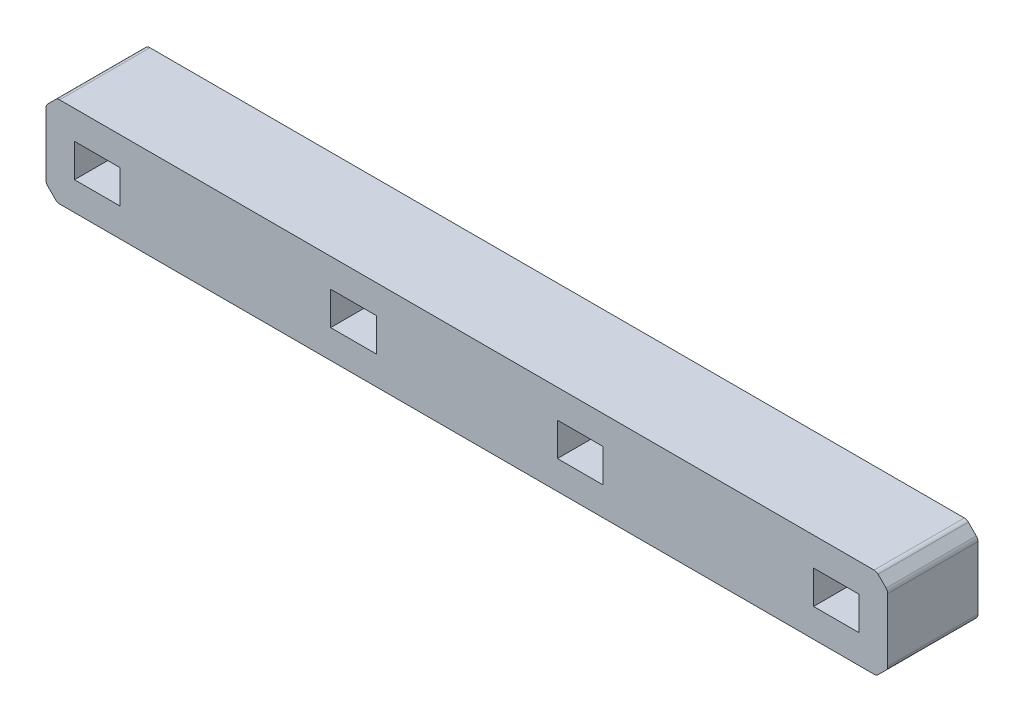
SolidWorks part; units mm, degrees
ref_plane "Front Plane" through (0, 0, 0) normal (0, 0, 1) x (1, 0, 0)
ref_plane "Top Plane" through (0, 0, 0) normal (0, 1, 0) x (1, 0, 0)
ref_plane "Right Plane" through (0, 0, 0) normal (1, 0, 0) x (0, 0, -1)
sketch "Sketch2" plane through (0, 0, 0) normal (0, 0, 1) x (1, 0, 0)
  line L1 (-186.5, 20) -> (186.5, 20)
  line L2 (-186.5, 20) -> (-186.5, -20)
  line L3 (-186.5, -20) -> (186.5, -20)
  line L4 (186.5, 20) -> (186.5, -20)
  line L5 (-186.5, 20) -> (186.5, -20) construction
  line L6 (-186.5, -20) -> (186.5, 20) construction
  point P0 (0, 0)
  dimension "D1" = 40
  dimension "D2" = 373
extrude "Boss-Extrude1" add sketch "Sketch2" along normal blind 40
sketch "Sketch3" plane through (0, 0, 40) normal (0, 0, 1) x (1, 0, 0)
  line L0 (22, 0) -> (-22, 0) construction
  line L6 (-153.625, -7.375) -> (-173.875, -7.375)
  line L8 (-153.625, -7.375) -> (-153.625, 7.375)
  line L9 (-40.125, -7.375) -> (-60.375, -7.375)
  line L10 (-40.125, -7.375) -> (-40.125, 7.375)
  line L11 (-40.125, 7.375) -> (-60.375, 7.375)
  line L12 (-60.375, -7.375) -> (-60.375, 7.375)
  line L13 (-40.125, -7.375) -> (-60.375, 7.375) construction
  line L14 (-40.125, 7.375) -> (-60.375, -7.375) construction
  line L15 (-153.625, 7.375) -> (-173.875, 7.375)
  line L16 (-173.875, -7.375) -> (-173.875, 7.375)
  line L17 (-153.625, -7.375) -> (-173.875, 7.375) construction
  line L18 (-153.625, 7.375) -> (-173.875, -7.375) construction
  line L19 (0, -22) -> (0, 22) construction
  line L20 (40.125, 7.375) -> (60.375, 7.375)
  line L21 (60.375, -7.375) -> (60.375, 7.375)
  line L22 (40.125, -7.375) -> (60.375, -7.375)
  line L23 (40.125, -7.375) -> (40.125, 7.375)
  line L24 (153.625, 7.375) -> (173.875, 7.375)
  line L25 (173.875, -7.375) -> (173.875, 7.375)
  line L26 (153.625, -7.375) -> (173.875, -7.375)
  line L27 (153.625, -7.375) -> (153.625, 7.375)
  line L28 (-186.5, 20) -> (-186.5, -20) construction
  point P0 (-163.75, 0)
  point P9 (-50.25, 0)
  dimension "D1" = 22.75
  dimension "D2" = 20.25
  dimension "D3" = 14.75
  dimension "D4" = 20.25
  dimension "D5" = 14.75
  dimension "D6" = 113.5
extrude "Cut-Extrude1" cut sketch "Sketch3" against normal through all
chamfer "Chamfer1" distance 5 angle 45 4 edges at (186.5, 20, 20) (186.5, -20, 20) (-186.5, -20, 20) (-186.5, 20, 20)
fillet "Fillet1" radius 2.5 8 edges at (181.5, 20, 20) (186.5, 15, 20) (186.5, -15, 20) (181.5, -20, 20) (-181.5, -20, 20) (-186.5, -15, 20) (-181.5, 20, 20) (-186.5, 15, 20)
equation "\"D2@Sketch2\"=133.5*2+55+25.5*2"
